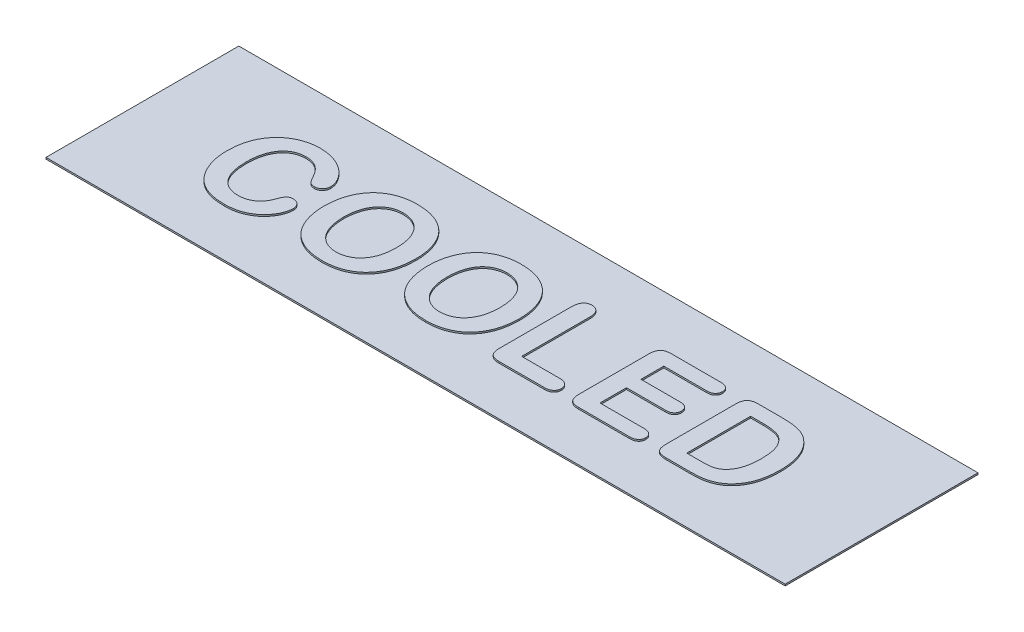
SolidWorks part; units mm, degrees
ref_plane "Front Plane" through (0, 0, 0) normal (0, 0, 1) x (1, 0, 0)
ref_plane "Top Plane" through (0, 0, 0) normal (0, 1, 0) x (1, 0, 0)
ref_plane "Right Plane" through (0, 0, 0) normal (1, 0, 0) x (0, 0, -1)
sketch "Sketch1" plane through (0, 0, 0) normal (0, 1, 0) x (1, 0, 0)
  line L1 (0, 0) -> (46, 0)
  line L2 (0, 0) -> (0, 12)
  line L3 (0, 12) -> (46, 12)
  line L4 (46, 0) -> (46, 12)
  line L5 (25.625, 8.2102) -> (25.625, 3.975)
  line L6 (25.625, 3.975) -> (28.0062, 3.975)
  line L7 (28.0062, 3) -> (25.1891, 3)
  line L8 (24.5, 3.723) -> (24.5, 8.2102)
  line L9 (33.2211, 7.875) -> (30.575, 7.875)
  line L10 (30.575, 7.875) -> (30.575, 6.45)
  line L11 (30.575, 6.45) -> (33.0113, 6.45)
  line L12 (33.0113, 5.55) -> (30.575, 5.55)
  line L13 (30.575, 5.55) -> (30.575, 3.9)
  line L14 (30.575, 3.9) -> (33.3125, 3.9)
  line L15 (33.3125, 3) -> (30.1391, 3)
  line L16 (29.45, 3.7172) -> (29.45, 8.0578)
  line L17 (30.1391, 8.775) -> (33.2211, 8.775)
  line L18 (35.5391, 8.775) -> (37.0777, 8.775)
  line L19 (37.1176, 3) -> (35.5918, 3)
  line L20 (34.85, 3.8238) -> (34.85, 8.0578)
  line L21 (35.975, 7.875) -> (35.975, 3.9)
  line L22 (35.975, 3.9) -> (36.8762, 3.9)
  line L23 (36.7602, 7.875) -> (35.975, 7.875)
  spline S0 degree 3 poles (10.5535, 4.8387) (10.5541, 4.7423) (10.5338, 4.5944) (10.4786, 4.3973) (10.4185, 4.2408) (10.342, 4.0813) (10.2429, 3.9236) (10.1257, 3.7666) (9.9892, 3.6122) (9.8331, 3.4657) (9.6548, 3.3334) (9.4567, 3.2157) (9.2392, 3.112) (9.0022, 3.0268) (8.649, 2.9461) (8.3708, 2.9243) (8.1805, 2.925) knots 0 0 0 0 0.085652 0.132259 0.182154 0.23476 0.289613 0.347798 0.409181 0.472952 0.538097 0.606611 0.677903 0.752531 0.830443 1 1 1 1
  spline S1 degree 3 poles (8.1805, 2.925) (8.0345, 2.9234) (7.8201, 2.9351) (7.5421, 2.9694) (7.3481, 3.0053) (7.1637, 3.0538) (6.9883, 3.1135) (6.8206, 3.1837) (6.6617, 3.2672) (6.5104, 3.3645) (6.3144, 3.5131) (6.18, 3.643) (6.0969, 3.7371) knots 0 0 0 0 0.189421 0.278349 0.363475 0.44526 0.525592 0.603756 0.681096 0.758174 0.837071 1 1 1 1
  spline S2 degree 3 poles (6.0969, 3.7371) (6.0205, 3.8301) (5.91, 3.9752) (5.7873, 4.1862) (5.6992, 4.3509) (5.6241, 4.5246) (5.557, 4.7036) (5.5003, 4.8886) (5.4554, 5.0798) (5.4182, 5.2764) (5.3866, 5.55) (5.373, 5.7582) (5.375, 5.8992) knots 0 0 0 0 0.155267 0.234286 0.31447 0.395866 0.478082 0.560751 0.645146 0.73117 0.818424 1 1 1 1
  spline S3 degree 3 poles (5.375, 5.8992) (5.3745, 6.1228) (5.3987, 6.4506) (5.4838, 6.8711) (5.5744, 7.1597) (5.6886, 7.4295) (5.8238, 7.6801) (5.9839, 7.9093) (6.1641, 8.1179) (6.3639, 8.3046) (6.5801, 8.4683) (6.8129, 8.6075) (7.0604, 8.7223) (7.3203, 8.8116) (7.681, 8.9015) (7.9613, 8.9243) (8.1488, 8.925) knots 0 0 0 0 0.14539 0.213117 0.278617 0.341813 0.403443 0.463501 0.52331 0.582458 0.641055 0.699407 0.758524 0.818232 0.877891 1 1 1 1
  spline S4 degree 3 poles (8.1488, 8.925) (8.263, 8.9242) (8.4326, 8.9172) (8.6542, 8.8867) (8.8138, 8.8563) (8.9687, 8.8181) (9.1185, 8.7695) (9.2633, 8.7125) (9.4025, 8.6463) (9.5357, 8.5755) (9.6609, 8.4991) (9.7788, 8.4196) (9.888, 8.3347) (9.9899, 8.2464) (10.0826, 8.1528) (10.169, 8.0571) (10.2454, 7.9563) (10.3146, 7.8554) (10.3732, 7.7539) (10.4234, 7.6544) (10.467, 7.5569) (10.4981, 7.4597) (10.5277, 7.3339) (10.5386, 7.2392) (10.5383, 7.1766) knots 0 0 0 0 0.105744 0.156826 0.206887 0.256081 0.304331 0.352537 0.400088 0.446834 0.492099 0.535821 0.578345 0.620111 0.660505 0.700198 0.739393 0.777399 0.813365 0.847806 0.880516 0.912073 0.942153 1 1 1 1
  spline S5 degree 3 poles (10.5383, 7.1766) (10.5367, 7.1128) (10.5224, 7.0145) (10.4587, 6.8998) (10.3977, 6.8207) (10.3237, 6.7543) (10.2119, 6.6882) (10.1159, 6.6679) (10.052, 6.6691) knots 0 0 0 0 0.247772 0.372489 0.502404 0.631547 0.75379 1 1 1 1
  spline S6 degree 3 poles (10.052, 6.6691) (9.9857, 6.6705) (9.8889, 6.678) (9.7767, 6.7264) (9.7092, 6.7764) (9.6512, 6.8454) (9.5634, 6.968) (9.5031, 7.0747) (9.4625, 7.152) knots 0 0 0 0 0.245524 0.349027 0.445511 0.551269 0.678784 1 1 1 1
  spline S7 degree 3 poles (9.4625, 7.152) (9.3915, 7.2868) (9.2736, 7.4761) (9.0783, 7.6855) (8.9263, 7.8107) (8.7587, 7.9075) (8.5057, 8.0035) (8.2973, 8.0231) (8.157, 8.025) knots 0 0 0 0 0.275111 0.398635 0.514745 0.628616 0.746036 1 1 1 1
  spline S8 degree 3 poles (8.157, 8.025) (8.0416, 8.0266) (7.8718, 8.0082) (7.6557, 7.9504) (7.5061, 7.888) (7.3651, 7.8099) (7.2339, 7.7126) (7.1127, 7.5976) (7.0001, 7.4664) (6.8995, 7.3187) (6.8129, 7.1557) (6.7383, 6.979) (6.6797, 6.7867) (6.6307, 6.5803) (6.5877, 6.2757) (6.5751, 6.039) (6.575, 5.877) knots 0 0 0 0 0.115013 0.169587 0.222731 0.276314 0.330118 0.385279 0.442791 0.502267 0.563316 0.626746 0.693334 0.763789 0.838279 1 1 1 1
  spline S9 degree 3 poles (6.575, 5.877) (6.5765, 5.7672) (6.5797, 5.6054) (6.6005, 5.3953) (6.622, 5.2484) (6.6469, 5.1085) (6.6798, 4.9763) (6.7189, 4.8512) (6.7626, 4.733) (6.8142, 4.6227) (6.867, 4.518) (6.9268, 4.4214) (6.9935, 4.3338) (7.0621, 4.2507) (7.1371, 4.1759) (7.2174, 4.1088) (7.33, 4.0289) (7.4827, 3.9466) (7.7523, 3.8499) (7.9701, 3.8249) (8.1172, 3.825) knots 0 0 0 0 0.113394 0.166879 0.217804 0.266602 0.313546 0.358313 0.401827 0.443509 0.483907 0.522846 0.560589 0.597505 0.634002 0.669781 0.70536 0.77645 0.848005 1 1 1 1
  spline S10 degree 3 poles (8.1172, 3.825) (8.1988, 3.8235) (8.3186, 3.8331) (8.4744, 3.8596) (8.5839, 3.888) (8.6895, 3.9226) (8.7889, 3.9679) (8.8845, 4.0193) (8.9749, 4.0791) (9.0594, 4.1477) (9.1391, 4.223) (9.2149, 4.3046) (9.2823, 4.3959) (9.3462, 4.4935) (9.4253, 4.6363) (9.474, 4.7512) (9.5023, 4.8305) knots 0 0 0 0 0.132859 0.195571 0.257351 0.317159 0.376451 0.435151 0.493965 0.552841 0.612306 0.672706 0.734094 0.79715 0.862714 1 1 1 1
  spline S11 degree 3 poles (9.5023, 4.8305) (9.5257, 4.9029) (9.5654, 5.0058) (9.6326, 5.1303) (9.6842, 5.2112) (9.7499, 5.2784) (9.867, 5.3457) (9.973, 5.3565) (10.0438, 5.3578) knots 0 0 0 0 0.27728 0.40012 0.51493 0.625576 0.739029 1 1 1 1
  spline S12 degree 3 poles (10.0438, 5.3578) (10.1104, 5.3587) (10.2093, 5.3388) (10.3284, 5.277) (10.4054, 5.2108) (10.4716, 5.1333) (10.5365, 5.0116) (10.5538, 4.908) (10.5535, 4.8387) knots 0 0 0 0 0.245889 0.366954 0.493336 0.619717 0.742738 1 1 1 1
  spline S13 degree 3 poles (14.2051, 8.925) (14.3507, 8.9255) (14.5656, 8.9134) (14.846, 8.8758) (15.0449, 8.8363) (15.2356, 8.7846) (15.4181, 8.7212) (15.5926, 8.6461) (15.7593, 8.5608) (15.9164, 8.4643) (16.0649, 8.3588) (16.2031, 8.2427) (16.3314, 8.117) (16.4488, 7.9814) (16.5572, 7.8367) (16.6557, 7.6821) (16.7432, 7.5175) (16.8218, 7.3454) (16.89, 7.1653) (16.947, 6.9781) (16.9944, 6.7833) (17.0302, 6.5813) (17.0647, 6.2975) (17.0765, 6.0804) (17.075, 5.9332) knots 0 0 0 0 0.092904 0.137184 0.180402 0.222249 0.263166 0.303591 0.343393 0.382556 0.421155 0.459552 0.497629 0.535619 0.573909 0.612912 0.652505 0.692776 0.733566 0.77528 0.817603 0.861416 0.906127 1 1 1 1
  spline S14 degree 3 poles (17.075, 5.9332) (17.0739, 5.7186) (17.0552, 5.4021) (16.9763, 4.9953) (16.8977, 4.7112) (16.7943, 4.4443) (16.6686, 4.1951) (16.5191, 3.9645) (16.3477, 3.753) (16.1549, 3.5616) (15.9394, 3.3947) (15.7026, 3.2523) (15.4465, 3.1323) (15.1697, 3.0379) (14.7635, 2.9505) (14.4457, 2.9228) (14.2285, 2.925) knots 0 0 0 0 0.137311 0.201924 0.26471 0.32552 0.384611 0.442946 0.500835 0.558413 0.616269 0.674654 0.73477 0.796775 0.861254 1 1 1 1
  spline S15 degree 3 poles (14.2285, 2.925) (14.012, 2.9254) (13.6934, 2.9499) (13.2866, 3.042) (13.0069, 3.1381) (12.748, 3.2605) (12.5089, 3.403) (12.2942, 3.5714) (12.1012, 3.7608) (11.9299, 3.9715) (11.7842, 4.2046) (11.6558, 4.4551) (11.5542, 4.7265) (11.4735, 5.0131) (11.3961, 5.418) (11.3756, 5.7306) (11.375, 5.9414) knots 0 0 0 0 0.138272 0.202996 0.265766 0.32667 0.385513 0.443075 0.500381 0.557823 0.616 0.67555 0.737189 0.800657 0.865406 1 1 1 1
  spline S16 degree 3 poles (11.375, 5.9414) (11.3743, 6.1559) (11.3971, 6.4722) (11.4778, 6.8802) (11.5621, 7.1662) (11.669, 7.4353) (11.7988, 7.6845) (11.949, 7.9131) (12.1208, 8.1206) (12.3143, 8.3058) (12.5284, 8.4678) (12.7621, 8.6072) (13.0155, 8.7218) (13.2873, 8.8137) (13.6834, 8.9028) (13.9941, 8.9248) (14.2051, 8.925) knots 0 0 0 0 0.138286 0.203794 0.267878 0.330279 0.39022 0.448768 0.506372 0.563563 0.621098 0.679161 0.738681 0.800098 0.863898 1 1 1 1
  spline S17 degree 3 poles (15.875, 5.9414) (15.875, 6.1434) (15.8532, 6.4387) (15.7652, 6.8118) (15.6893, 7.0219) (15.6164, 7.1776) (15.5569, 7.286) (15.4929, 7.388) (15.4202, 7.4803) (15.3448, 7.5672) (15.2631, 7.6468) (15.1751, 7.7177) (15.0518, 7.8039) (14.8857, 7.8931) (14.5954, 7.9971) (14.3621, 8.0252) (14.2051, 8.025) knots 0 0 0 0 0.20134 0.293363 0.381131 0.423258 0.464531 0.504255 0.543094 0.58142 0.618845 0.656464 0.693922 0.768612 0.843449 1 1 1 1
  spline S18 degree 3 poles (14.2051, 8.025) (14.0914, 8.0257) (13.9227, 8.0088) (13.7066, 7.9518) (13.5537, 7.8931) (13.4093, 7.8181) (13.2744, 7.727) (13.1503, 7.6202) (13.0366, 7.4982) (12.9338, 7.3596) (12.8425, 7.2031) (12.7631, 7.0286) (12.6953, 6.8378) (12.6418, 6.6316) (12.5895, 6.3323) (12.5754, 6.0996) (12.575, 5.9414) knots 0 0 0 0 0.114496 0.169875 0.224704 0.279284 0.333437 0.388431 0.443857 0.501251 0.561945 0.626059 0.694164 0.765773 0.840522 1 1 1 1
  spline S19 degree 3 poles (12.575, 5.9414) (12.5754, 5.7816) (12.5895, 5.5466) (12.642, 5.2439) (12.6951, 5.0343) (12.764, 4.8398) (12.8466, 4.6621) (12.9392, 4.4999) (13.0485, 4.3577) (13.1666, 4.2323) (13.2934, 4.1231) (13.4282, 4.03) (13.5721, 3.9542) (13.7245, 3.8974) (13.9392, 3.8391) (14.1081, 3.8257) (14.2215, 3.825) knots 0 0 0 0 0.159004 0.23357 0.305398 0.373868 0.438553 0.500211 0.559287 0.616472 0.671316 0.72554 0.779084 0.832715 0.887016 1 1 1 1
  spline S20 degree 3 poles (14.2215, 3.825) (14.3674, 3.8239) (14.5852, 3.8529) (14.8593, 3.9498) (15.0209, 4.0323) (15.1427, 4.1137) (15.2308, 4.1824) (15.3126, 4.2605) (15.3906, 4.3451) (15.4629, 4.438) (15.5313, 4.538) (15.5945, 4.6461) (15.653, 4.7619) (15.7058, 4.8851) (15.7518, 5.0153) (15.7885, 5.1531) (15.8206, 5.2972) (15.8449, 5.4487) (15.8686, 5.6638) (15.8751, 5.8292) (15.875, 5.9414) knots 0 0 0 0 0.144679 0.215804 0.287769 0.324117 0.361116 0.398418 0.436289 0.475227 0.515125 0.556487 0.59949 0.643783 0.6894 0.73643 0.785257 0.835932 0.888598 1 1 1 1
  spline S21 degree 3 poles (20.6551, 8.925) (20.8007, 8.9255) (21.0156, 8.9134) (21.296, 8.8758) (21.4949, 8.8363) (21.6856, 8.7846) (21.8681, 8.7212) (22.0426, 8.6461) (22.2093, 8.5608) (22.3664, 8.4643) (22.5149, 8.3588) (22.6531, 8.2427) (22.7814, 8.117) (22.8988, 7.9814) (23.0072, 7.8367) (23.1057, 7.6821) (23.1932, 7.5175) (23.2718, 7.3454) (23.34, 7.1653) (23.397, 6.9781) (23.4444, 6.7833) (23.4802, 6.5813) (23.5147, 6.2975) (23.5265, 6.0804) (23.525, 5.9332) knots 0 0 0 0 0.092904 0.137184 0.180402 0.222249 0.263166 0.303591 0.343393 0.382556 0.421155 0.459552 0.497629 0.535619 0.573909 0.612912 0.652505 0.692776 0.733566 0.77528 0.817603 0.861416 0.906127 1 1 1 1
  spline S22 degree 3 poles (23.525, 5.9332) (23.5239, 5.7186) (23.5052, 5.4021) (23.4263, 4.9953) (23.3477, 4.7112) (23.2443, 4.4443) (23.1186, 4.1951) (22.9691, 3.9645) (22.7977, 3.753) (22.6049, 3.5616) (22.3894, 3.3947) (22.1526, 3.2523) (21.8965, 3.1323) (21.6197, 3.0379) (21.2135, 2.9505) (20.8957, 2.9228) (20.6785, 2.925) knots 0 0 0 0 0.137311 0.201924 0.26471 0.32552 0.384611 0.442946 0.500835 0.558413 0.616269 0.674654 0.73477 0.796775 0.861254 1 1 1 1
  spline S23 degree 3 poles (20.6785, 2.925) (20.462, 2.9254) (20.1434, 2.9499) (19.7366, 3.042) (19.4569, 3.1381) (19.198, 3.2605) (18.9589, 3.403) (18.7442, 3.5714) (18.5512, 3.7608) (18.3799, 3.9715) (18.2342, 4.2046) (18.1058, 4.4551) (18.0042, 4.7265) (17.9235, 5.0131) (17.8461, 5.418) (17.8256, 5.7306) (17.825, 5.9414) knots 0 0 0 0 0.138272 0.202996 0.265766 0.32667 0.385513 0.443075 0.500381 0.557823 0.616 0.67555 0.737189 0.800657 0.865406 1 1 1 1
  spline S24 degree 3 poles (17.825, 5.9414) (17.8243, 6.1559) (17.8471, 6.4722) (17.9278, 6.8802) (18.0121, 7.1662) (18.119, 7.4353) (18.2488, 7.6845) (18.399, 7.9131) (18.5708, 8.1206) (18.7643, 8.3058) (18.9784, 8.4678) (19.2121, 8.6072) (19.4655, 8.7218) (19.7373, 8.8137) (20.1334, 8.9028) (20.4441, 8.9248) (20.6551, 8.925) knots 0 0 0 0 0.138286 0.203794 0.267878 0.330279 0.39022 0.448768 0.506372 0.563563 0.621098 0.679161 0.738681 0.800098 0.863898 1 1 1 1
  spline S25 degree 3 poles (22.325, 5.9414) (22.325, 6.1434) (22.3032, 6.4387) (22.2152, 6.8118) (22.1393, 7.0219) (22.0664, 7.1776) (22.0069, 7.286) (21.9429, 7.388) (21.8702, 7.4803) (21.7948, 7.5672) (21.7131, 7.6468) (21.6251, 7.7177) (21.5018, 7.8039) (21.3357, 7.8931) (21.0454, 7.9971) (20.8121, 8.0252) (20.6551, 8.025) knots 0 0 0 0 0.20134 0.293363 0.381131 0.423258 0.464531 0.504255 0.543094 0.58142 0.618845 0.656464 0.693922 0.768612 0.843449 1 1 1 1
  spline S26 degree 3 poles (20.6551, 8.025) (20.5414, 8.0257) (20.3727, 8.0088) (20.1566, 7.9518) (20.0037, 7.8931) (19.8593, 7.8181) (19.7244, 7.727) (19.6003, 7.6202) (19.4866, 7.4982) (19.3838, 7.3596) (19.2925, 7.2031) (19.2131, 7.0286) (19.1453, 6.8378) (19.0918, 6.6316) (19.0395, 6.3323) (19.0254, 6.0996) (19.025, 5.9414) knots 0 0 0 0 0.114496 0.169875 0.224704 0.279284 0.333437 0.388431 0.443857 0.501251 0.561945 0.626059 0.694164 0.765773 0.840522 1 1 1 1
  spline S27 degree 3 poles (19.025, 5.9414) (19.0254, 5.7816) (19.0395, 5.5466) (19.092, 5.2439) (19.1451, 5.0343) (19.214, 4.8398) (19.2966, 4.6621) (19.3892, 4.4999) (19.4985, 4.3577) (19.6166, 4.2323) (19.7434, 4.1231) (19.8782, 4.03) (20.0221, 3.9542) (20.1745, 3.8974) (20.3892, 3.8391) (20.5581, 3.8257) (20.6715, 3.825) knots 0 0 0 0 0.159004 0.23357 0.305398 0.373868 0.438553 0.500211 0.559287 0.616472 0.671316 0.72554 0.779084 0.832715 0.887016 1 1 1 1
  spline S28 degree 3 poles (20.6715, 3.825) (20.8174, 3.8239) (21.0352, 3.8529) (21.3093, 3.9498) (21.4709, 4.0323) (21.5927, 4.1137) (21.6808, 4.1824) (21.7626, 4.2605) (21.8406, 4.3451) (21.9129, 4.438) (21.9813, 4.538) (22.0445, 4.6461) (22.103, 4.7619) (22.1558, 4.8851) (22.2018, 5.0153) (22.2385, 5.1531) (22.2706, 5.2972) (22.2949, 5.4487) (22.3186, 5.6638) (22.3251, 5.8292) (22.325, 5.9414) knots 0 0 0 0 0.144679 0.215804 0.287769 0.324117 0.361116 0.398418 0.436289 0.475227 0.515125 0.556487 0.59949 0.643783 0.6894 0.73643 0.785257 0.835932 0.888598 1 1 1 1
  spline S29 degree 3 poles (28.0062, 3.975) (28.0913, 3.9763) (28.2138, 3.9613) (28.3598, 3.9013) (28.4442, 3.8379) (28.5122, 3.7636) (28.5791, 3.6493) (28.5955, 3.5497) (28.5957, 3.484) knots 0 0 0 0 0.29564 0.422721 0.544076 0.659398 0.770688 1 1 1 1
  spline S30 degree 3 poles (28.5957, 3.484) (28.5959, 3.4175) (28.5794, 3.3171) (28.5128, 3.2027) (28.4457, 3.13) (28.3613, 3.07) (28.2147, 3.0134) (28.0921, 2.9988) (28.0062, 3) knots 0 0 0 0 0.232558 0.344108 0.456772 0.574921 0.701249 1 1 1 1
  spline S31 degree 3 poles (25.1891, 3) (25.0828, 2.9988) (24.9313, 3.0154) (24.7545, 3.0892) (24.656, 3.1673) (24.5834, 3.2714) (24.5121, 3.4554) (24.5022, 3.6134) (24.5, 3.723) knots 0 0 0 0 0.275852 0.38874 0.49248 0.597007 0.713775 1 1 1 1
  spline S32 degree 3 poles (24.5, 8.2102) (24.4999, 8.3151) (24.513, 8.466) (24.5812, 8.6439) (24.6485, 8.7471) (24.7332, 8.8266) (24.8644, 8.9056) (24.9804, 8.9239) (25.0566, 8.925) knots 0 0 0 0 0.308898 0.436927 0.555089 0.666891 0.774722 1 1 1 1
  spline S33 degree 3 poles (25.0566, 8.925) (25.1353, 8.9269) (25.2516, 8.9044) (25.3869, 8.8285) (25.4727, 8.7491) (25.5434, 8.6475) (25.6122, 8.468) (25.6253, 8.316) (25.625, 8.2102) knots 0 0 0 0 0.227639 0.335766 0.446489 0.563783 0.691981 1 1 1 1
  spline S34 degree 3 poles (33.0113, 6.45) (33.09, 6.448) (33.2047, 6.4406) (33.338, 6.3851) (33.4144, 6.3307) (33.4731, 6.2631) (33.5323, 6.1576) (33.5456, 6.0649) (33.5457, 6.0035) knots 0 0 0 0 0.301571 0.427298 0.5443 0.654763 0.765066 1 1 1 1
  spline S35 degree 3 poles (33.5457, 6.0035) (33.5462, 5.9418) (33.5312, 5.8498) (33.4742, 5.7424) (33.4161, 5.6733) (33.3403, 5.6169) (33.2065, 5.56) (33.0909, 5.5514) (33.0113, 5.55) knots 0 0 0 0 0.233451 0.343652 0.455654 0.571599 0.697115 1 1 1 1
  spline S36 degree 3 poles (33.3125, 3.9) (33.3934, 3.8977) (33.5122, 3.8909) (33.6503, 3.8341) (33.7308, 3.7793) (33.7944, 3.7119) (33.8543, 3.6031) (33.872, 3.5098) (33.8703, 3.4465) knots 0 0 0 0 0.301115 0.428958 0.546002 0.658095 0.767064 1 1 1 1
  spline S37 degree 3 poles (33.8703, 3.4465) (33.8725, 3.3849) (33.8536, 3.2943) (33.7941, 3.1879) (33.7308, 3.1208) (33.6505, 3.0656) (33.5114, 3.0118) (33.394, 3.0004) (33.3125, 3) knots 0 0 0 0 0.227881 0.33652 0.449574 0.567623 0.696013 1 1 1 1
  spline S38 degree 3 poles (30.1391, 3) (30.0333, 3.0003) (29.881, 3.0136) (29.705, 3.0883) (29.6056, 3.1649) (29.5338, 3.2688) (29.4619, 3.4512) (29.4523, 3.6084) (29.45, 3.7172) knots 0 0 0 0 0.276681 0.389999 0.493502 0.598427 0.714697 1 1 1 1
  spline S39 degree 3 poles (29.45, 8.0578) (29.4507, 8.1342) (29.4565, 8.2443) (29.487, 8.3814) (29.5188, 8.4682) (29.5595, 8.5446) (29.6122, 8.6092) (29.6753, 8.6623) (29.748, 8.7054) (29.8317, 8.7362) (29.9614, 8.7697) (30.0668, 8.7734) (30.1391, 8.775) knots 0 0 0 0 0.198924 0.285459 0.364561 0.438696 0.509487 0.580148 0.652133 0.728383 0.811204 1 1 1 1
  spline S40 degree 3 poles (33.2211, 8.775) (33.3026, 8.7722) (33.4223, 8.7667) (33.56, 8.709) (33.6397, 8.6547) (33.6997, 8.5864) (33.7618, 8.4818) (33.7753, 8.3887) (33.7754, 8.3273) knots 0 0 0 0 0.306655 0.434289 0.551174 0.662301 0.769708 1 1 1 1
  spline S41 degree 3 poles (33.7754, 8.3273) (33.7758, 8.2646) (33.7612, 8.1703) (33.7004, 8.0627) (33.6396, 7.9942) (33.5602, 7.9396) (33.4216, 7.8843) (33.3029, 7.8771) (33.2211, 7.875) knots 0 0 0 0 0.233121 0.34237 0.452806 0.568964 0.695252 1 1 1 1
  spline S42 degree 3 poles (37.0777, 8.775) (37.2638, 8.7738) (37.5333, 8.7649) (37.8759, 8.7174) (38.1043, 8.6719) (38.3175, 8.6054) (38.5887, 8.4875) (38.7729, 8.3605) (38.8871, 8.2652) knots 0 0 0 0 0.290636 0.419884 0.539455 0.653804 0.767646 1 1 1 1
  spline S43 degree 3 poles (38.8871, 8.2652) (38.962, 8.1998) (39.0702, 8.0972) (39.1992, 7.9461) (39.2881, 7.8264) (39.3703, 7.7008) (39.4455, 7.569) (39.514, 7.4307) (39.5727, 7.2848) (39.6276, 7.134) (39.6722, 6.9762) (39.7132, 6.8132) (39.7437, 6.6427) (39.7702, 6.4666) (39.7933, 6.2189) (39.8001, 6.0298) (39.8, 5.9016) knots 0 0 0 0 0.113993 0.170501 0.227433 0.284661 0.342396 0.401245 0.461255 0.522553 0.585016 0.649063 0.715076 0.783373 0.853071 1 1 1 1
  spline S44 degree 3 poles (39.8, 5.9016) (39.7988, 5.7347) (39.7912, 5.4886) (39.7509, 5.1702) (39.7114, 4.9474) (39.6601, 4.7358) (39.5959, 4.5351) (39.5181, 4.3452) (39.4277, 4.1659) (39.3256, 3.9956) (39.1688, 3.7818) (39.0341, 3.6345) (38.9352, 3.5449) knots 0 0 0 0 0.193526 0.284763 0.37169 0.455568 0.536879 0.615643 0.693177 0.769333 0.845479 1 1 1 1
  spline S45 degree 3 poles (38.9352, 3.5449) (38.8586, 3.4784) (38.7365, 3.3878) (38.5623, 3.2852) (38.4259, 3.2198) (38.2848, 3.1637) (38.139, 3.1151) (37.9878, 3.0767) (37.8308, 3.0473) (37.6664, 3.0267) (37.4282, 3.0059) (37.2438, 3.0004) (37.1176, 3) knots 0 0 0 0 0.156627 0.234241 0.311963 0.389947 0.468751 0.549095 0.630751 0.715322 0.804967 1 1 1 1
  spline S46 degree 3 poles (35.5918, 3) (35.4978, 2.9986) (35.3656, 3.0099) (35.2042, 3.0488) (35.1109, 3.092) (35.0357, 3.147) (34.9745, 3.2112) (34.9279, 3.2853) (34.896, 3.3703) (34.8766, 3.4662) (34.8548, 3.6179) (34.8507, 3.739) (34.85, 3.8238) knots 0 0 0 0 0.215218 0.30322 0.379365 0.449245 0.515784 0.5814 0.648612 0.722944 0.805292 1 1 1 1
  spline S47 degree 3 poles (34.85, 8.0578) (34.8507, 8.1671) (34.8639, 8.3233) (34.9343, 8.5065) (35.0085, 8.6088) (35.1074, 8.6854) (35.2821, 8.7621) (35.4343, 8.774) (35.5391, 8.775) knots 0 0 0 0 0.285971 0.402433 0.507304 0.610976 0.724896 1 1 1 1
  spline S48 degree 3 poles (36.8762, 3.9) (36.9644, 3.9008) (37.0891, 3.9009) (37.2442, 3.9074) (37.3691, 3.9162) (37.5176, 3.9406) (37.6629, 3.9827) (37.7775, 4.0286) (37.8853, 4.0836) (37.958, 4.1367) (38.0023, 4.1754) knots 0 0 0 0 0.223182 0.315098 0.392345 0.53942 0.694723 0.773569 0.851294 1 1 1 1
  spline S49 degree 3 poles (38.0023, 4.1754) (38.1051, 4.2597) (38.2369, 4.416) (38.3725, 4.6575) (38.4573, 4.8644) (38.5203, 5.0945) (38.5852, 5.4434) (38.5997, 5.7195) (38.6, 5.9098) knots 0 0 0 0 0.209904 0.320807 0.437978 0.56343 0.698232 1 1 1 1
  spline S50 degree 3 poles (38.6, 5.9098) (38.6017, 6.0456) (38.5921, 6.2424) (38.5665, 6.4954) (38.5363, 6.6645) (38.5014, 6.8209) (38.4551, 6.9628) (38.4031, 7.0922) (38.3402, 7.2071) (38.272, 7.3104) (38.2002, 7.4036) (38.125, 7.4871) (38.0467, 7.5618) (37.9629, 7.625) (37.8758, 7.6792) (37.7852, 7.7248) (37.6555, 7.7694) (37.4822, 7.8118) (37.173, 7.8643) (36.9287, 7.8749) (36.7602, 7.875) knots 0 0 0 0 0.129301 0.18771 0.24211 0.292941 0.340261 0.384153 0.425623 0.464852 0.502003 0.537582 0.571813 0.605015 0.637447 0.669407 0.70143 0.767873 0.839223 1 1 1 1
  dimension "D3" = 12
  dimension "D4" = 46
extrude "Boss-Extrude1" add sketch "Sketch1" against normal blind 0.1 contours L1 L4 L3 L2 S40 S41 L9 L10 L11 S34 S35 L12 L13 L14 S36 S37 L15 S38 L16 S39 L17 S32 S33 L5 L6 S29 S30 L7 S31 L8 S23 S24 S21 S22 S15 S16 S13 S14 S11 S12 S0 S1 S2 S3 S4 S5 | S12 S11 S10 S9 S8 S7 S6 S5 S4 S3 S2 S1 S0 | S16 S15 S14 S13 S20 S19 S18 S17 | S19 S20 S17 S18 | S24 S23 S22 S21 S28 S27 S26 S25 | S27 S28 S25 S26 | S33 S32 L8 S31 L7 S30 S29 L6 L5 | S41 S40 L17 S39 L16 S38 L15 S37 S36 L14 L13 L12 S35 S34 L11 L10 L9 | S49 S50 L23 L21 L22 S48 | S47 L20 S46 L19 S45 S44 S43 S42 L18 S50 S49 S48 L22 L21 L23 region at (0.4754, 0, -6) region at (25.553, 0, -6.0926) region at (31.2019, 0, -5.8935) region at (36.3084, 0, -8.6989) region at (37.1795, 0, -5.8853) region at (9.7124, 0, -3.4762) region at (16.2767, 0, -8.0507) region at (14.2249, 0, -5.9287) region at (22.7267, 0, -8.0507) region at (20.6749, 0, -5.9287)
extrude "Boss-Extrude2" add sketch "Sketch1<7>" along normal blind 0.1 separate body contours S12 S11 S10 S9 S8 S7 S6 S5 S4 S3 S2 S1 S0 | S16 S15 S14 S13 S20 S19 S18 S17 | S24 S23 S22 S21 S28 S27 S26 S25 | S33 S32 L8 S31 L7 S30 S29 L6 L5 | S41 S40 L17 S39 L16 S38 L15 S37 S36 L14 L13 L12 S35 S34 L11 L10 L9 | S47 L20 S46 L19 S45 S44 S43 S42 L18 S50 S49 S48 L22 L21 L23 region at (25.553, 0, -6.0926) region at (31.2019, 0, -5.8935) region at (36.3084, 0, -8.6989) region at (9.7124, 0, -3.4762) region at (16.2767, 0, -8.0507) region at (22.7267, 0, -8.0507)
sketch "Sketch1<7>" plane through (0, 0, 0) normal (0, 1, 0) x (1, 0, 0) same geometry as "Sketch1"
sketch "Sketch2" plane through (0, 0, 0) normal (0, 1, 0) x (1, 0, 0)
  line L0 (23, 12) -> (23, 0) construction
  line L1 (0, 12) -> (46, 12) construction
  line L2 (0, 0) -> (46, 0) construction
ref_plane "Plane1" through (23, 0, 0) normal (1, 0, 0) x (0, 0, -1)
